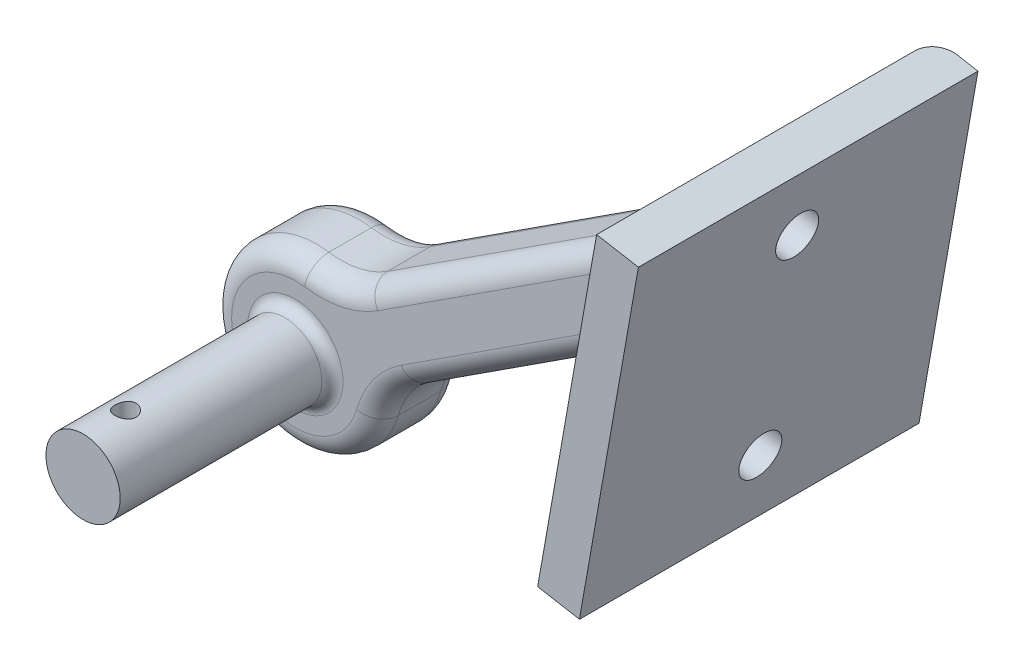
SolidWorks part; units mm, degrees
material "Cast Alloy Steel"
ref_plane "Front" through (0, 0, 0) normal (0, 0, 1) x (1, 0, 0)
ref_plane "Top" through (0, 0, 0) normal (0, 1, 0) x (1, 0, 0)
ref_plane "Right" through (0, 0, 0) normal (1, 0, 0) x (0, 0, -1)
sketch "Sketch1" plane through (0, 0, 0) normal (0, 0, 1) x (1, 0, 0)
  line L0 (0, 0) -> (25.4, 144.0506) construction
  line L1 (25.4, 144.0506) -> (25.4, 0) construction
  line L2 (25.4, 0) -> (0, 0) construction
  line L3 (4.4107, 25.0141) -> (-1.8429, 26.1168)
  line L4 (-1.8429, 26.1168) -> (6.9785, 76.145)
  line L5 (6.9785, 76.145) -> (13.232, 75.0424)
  line L6 (13.232, 75.0424) -> (4.4107, 25.0141)
  line L7 (-76.2, 0) -> (2.5678, 51.1309) construction
  circle A0 centre (-76.2, 0) radius 12.7
  dimension "D1" = 25.4
  dimension "D2" = 76.2
  dimension "D3" = 50.8
  dimension "D4" = 25.4
  dimension "D5" = 6.35
  dimension "D6" = 10
  dimension "D7" = 25.4
sketch "Sketch2" plane through (0, 0, 0) normal (0, 0, 1) x (1, 0, 0)
  line L0 (-1.8429, 26.1168) -> (6.9785, 76.145) construction
  line L1 (1.0604, 42.5818) -> (4.0752, 59.68)
  line L2 (-56.7711, 12.612) -> (60.7287, 88.8851) construction
  line L3 (-76.2, 0) -> (2.5678, 51.1309) construction
  line L4 (-70.4321, 11.3147) -> (4.0752, 59.68)
  line L5 (-63.5173, 0.6622) -> (1.0604, 42.5818)
  circle A0 centre (-76.2, 0) radius 12.7 construction
  arc A1 (-70.4321, 11.3147) -> (-63.5173, 0.6622) centre (-76.2, 0) ccw
  dimension "D1" = 12.7
extrude "Base-Extrude" add sketch "Sketch2" along normal blind 12.7
sketch "Sketch3" plane through (0, 0, 0) normal (0, 0, 1) x (1, 0, 0)
  line L4 (4.4107, 25.0141) -> (-1.8429, 26.1168)
  line L5 (13.232, 75.0424) -> (4.4107, 25.0141)
  line L6 (6.9785, 76.145) -> (13.232, 75.0424)
  line L7 (-1.8429, 26.1168) -> (6.9785, 76.145)
  line L8 (4.4107, 25.0141) -> (-1.8429, 26.1168)
  line L9 (13.232, 75.0424) -> (4.4107, 25.0141)
  line L10 (6.9785, 76.145) -> (13.232, 75.0424)
  line L11 (-1.8429, 26.1168) -> (6.9785, 76.145)
  dimension "D1" = 0
extrude "Boss-Extrude1" add sketch "Sketch3" along normal blind 50.8
fillet "Fillet1" radius 12.7 2 edges at (-63.5173, 0.6622, 6.35) (-70.4321, 11.3147, 6.35)
sketch "Sketch5" plane through (-6.2535, 1.1027, 0) normal (-0.9848, 0.1736, 0) x (0, 0, 1)
  line L0 (25.4, 76.2) -> (25.4, 25.4) construction
  line L1 (50.8, 76.2) -> (0, 76.2) construction
  line L2 (50.8, 25.4) -> (0, 25.4) construction
  circle A0 centre (25.4, 66.675) radius 3.175
  circle A1 centre (25.4, 34.925) radius 3.175
  dimension "D3" = 6.35
  dimension "D4" = 6.35
  dimension "D1" = 9.525
  dimension "D2" = 9.525
extrude "Cut-Extrude2" cut sketch "Sketch5" against normal through all
fillet "Fillet4" radius 9.525 2 edges at (4.0752, 59.68, 6.35) (1.0604, 42.5818, 6.35)
fillet "Fillet5" radius 3.175 15 edges at (3.3566, 60.1558, 12.7) (-7.6778, 32.3485, 0) (-32.4826, 35.9491, 12.7) (-37.4064, 17.6117, 0) (-69.7784, 12.717, 12.7) (-61.9703, 0.6885, 0) (-86.8524, -6.9149, 12.7) (-86.8524, -6.9149, 0) (5.8865, 69.9524, 0) (-61.9703, 0.6885, 12.7) (-7.6778, 32.3485, 12.7) (-69.7784, 12.717, 0) (3.3566, 60.1558, 0) (-37.4064, 17.6117, 12.7) (-32.4826, 35.9491, 0)
sketch "Sketch6" plane through (0, 0, 12.7) normal (0, 0, 1) x (1, 0, 0)
  circle A0 centre (-76.2, 0) radius 5.5563
  dimension "D1" = 11.1125
extrude "Boss-Extrude2" add sketch "Sketch6" along normal blind 31.75
fillet "Fillet9" radius 1.5875 4 edges at (-1.6488, 27.2176, 11.3088) (3.8228, 58.2485, 12.236) (1.195, 43.3451, 12.7) (-70.6438, 0, 12.7)
sketch "Sketch7" plane through (0, 0, 0) normal (0, 1, 0) x (1, 0, 0)
  line L0 (-76.2, -9.525) -> (-76.2, -3.175) construction
  line L1 (1.5012, -12.7) -> (-63.8369, -12.7) construction
  circle A0 centre (-76.2, -38.1) radius 1.5875
  dimension "D1" = 3.175
  dimension "D2" = 25.4
extrude "Cut-Extrude3" cut sketch "Sketch7" along normal through all and the other way through all
